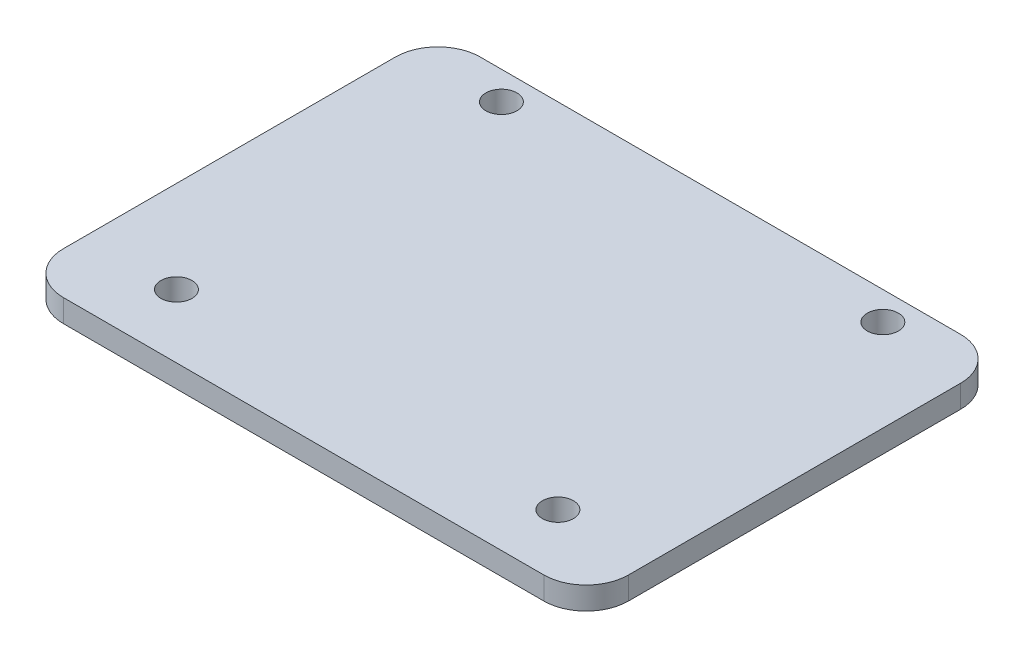
SolidWorks part; units mm, degrees
material "Oshpark board"
ref_plane "Front Plane" through (0, 0, 0) normal (0, 0, 1) x (1, 0, 0)
ref_plane "Top Plane" through (0, 0, 0) normal (0, 1, 0) x (1, 0, 0)
ref_plane "Right Plane" through (0, 0, 0) normal (1, 0, 0) x (0, 0, -1)
sketch "Sketch1" plane through (0, 0, 0) normal (0, 1, 0) x (1, 0, 0)
  line L0 (-20, 14.75) -> (20, -14.75) construction
  line L1 (-20, 14.75) -> (20, 14.75)
  line L2 (-20, 14.75) -> (-20, -14.75)
  line L3 (-20, -14.75) -> (20, -14.75)
  line L4 (20, 14.75) -> (20, -14.75)
  dimension "D1" = 40
  dimension "D2" = 29.5
extrude "Boss-Extrude1" add sketch "Sketch1" along normal blind 1.6
hole_wizard "M2 Clearance Hole1" positions "Sketch2" profile "Sketch3" hole size "M2" standard "ANSI Metric"
sketch "Sketch2" plane through (0, 1.6, 0) normal (0, 1, 0) x (1, 0, 0)
  line L1 (-13.5, 12.75) -> (13.5, 12.75)
  line L2 (-13.5, 12.75) -> (-13.5, -10.25)
  line L3 (-13.5, -10.25) -> (13.5, -10.25)
  line L4 (13.5, 12.75) -> (13.5, -10.25)
  line L5 (-20, -14.75) -> (20, -14.75) construction
  point P0 (-13.5, 12.75)
  point P2 (13.5, 12.75)
  point P4 (13.5, -10.25)
  point P6 (-13.5, -10.25)
  point P142 (0, -10.25)
  dimension "D1" = 23
  dimension "D2" = 27
  dimension "D3" = 4.5
sketch "Sketch3" plane through (-13.5, 1.6, -12.75) normal (1, 0, 0) x (0, 0, 1)
  line L0 (0, 0) -> (0, 5.8609)
  line L1 (0, 5.8609) -> (1.1, 5.2)
  line L2 (1.1, 5.2) -> (1.1, 0)
  line L5 (1.1, 0) -> (0, 0)
  line L10 (0, 5.8609) -> (-1.1, 5.2) construction
  line L11 (0, -6.35) -> (0, 107.95) construction
  dimension "Hole Dia." = 2.2
  dimension "Hole Depth" = 5.2
  dimension "Drill Angle" = 118
fillet "Fillet1" radius 3 4 edges at (20, 0.8, -14.75) (20, 0.8, 14.75) (-20, 0.8, 14.75) (-20, 0.8, -14.75)
sketch "Sketch4" plane through (0, 0, 0) normal (0, -1, 0) x (1, 0, 0)
  line L0 (-2.2, -5.8223) -> (2.2, -5.8223) construction
  line L1 (-2.2, -0.8223) -> (-2.2, -5.8223) construction
  line L2 (2.2, -0.8223) -> (-2.2, -0.8223) construction
  line L3 (2.2, -5.8223) -> (2.2, -0.8223) construction
  line L12 (-2.2, -5.8223) -> (2.2, -5.8223)
  line L13 (-2.2, -0.8223) -> (-2.2, -5.8223)
  line L14 (2.2, -0.8223) -> (-2.2, -0.8223)
  line L15 (2.2, -5.8223) -> (2.2, -0.8223)
  circle A0 centre (0, -3.3223) radius 0.75 construction
  circle A1 centre (0, -3.3223) radius 0.75
  circle A2 centre (0, -3.3223) radius 3 construction
  circle A3 centre (0, -3.3223) radius 3
